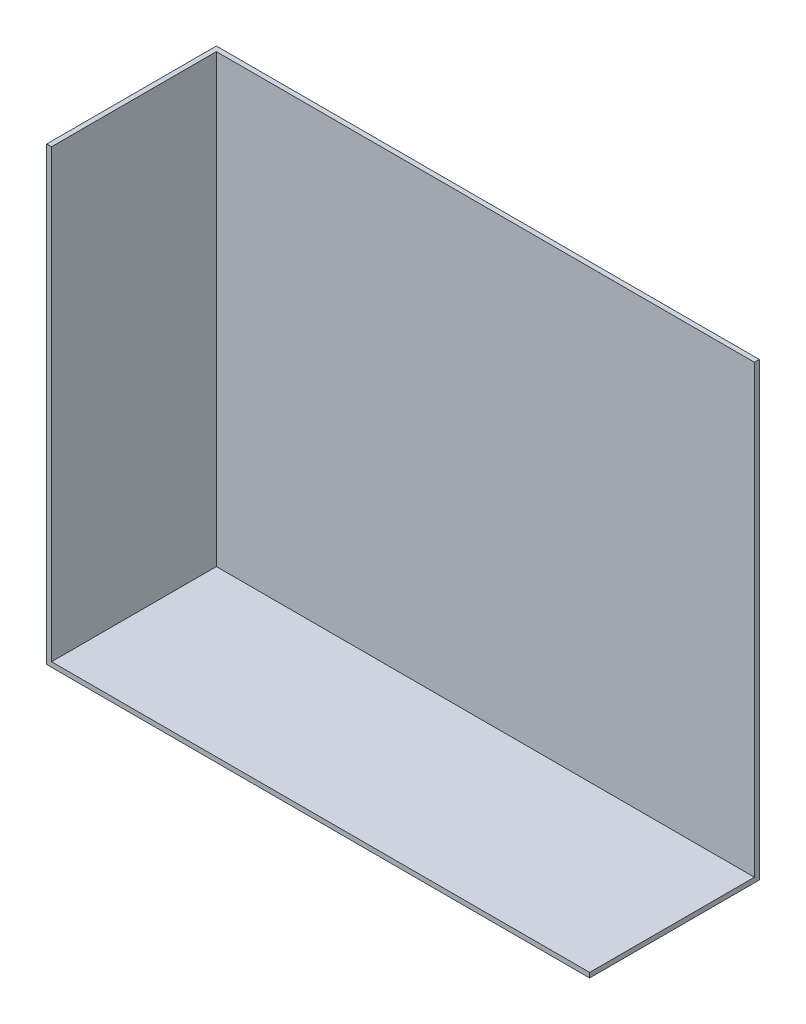
SolidWorks part; units mm, degrees
ref_plane "Front Plane" through (0, 0, 0) normal (0, 0, 1) x (1, 0, 0)
ref_plane "Top Plane" through (0, 0, 0) normal (0, 1, 0) x (1, 0, 0)
ref_plane "Right Plane" through (0, 0, 0) normal (1, 0, 0) x (0, 0, -1)
sketch "Sketch1" plane through (0, 0, 0) normal (0, 1, 0) x (1, 0, 0)
  line L1 (1422.4, 444.5) -> (-1422.4, 444.5)
  line L2 (1422.4, 444.5) -> (1422.4, -444.5)
  line L3 (1422.4, -444.5) -> (-1422.4, -444.5)
  line L4 (-1422.4, 444.5) -> (-1422.4, -444.5)
  line L5 (1422.4, 444.5) -> (-1422.4, -444.5) construction
  line L6 (1422.4, -444.5) -> (-1422.4, 444.5) construction
  point P0 (0, 0)
  dimension "D1" = 2844.8
  dimension "D2" = 889
extrude "Boss-Extrude1" add sketch "Sketch1" along normal blind 2362.2
shell "Shell1" thickness 25.4 removed face at (0, 2362.2, 0) removed face at (0, 1181.1, 444.5) removed face at (1422.4, 1181.1, 0)
